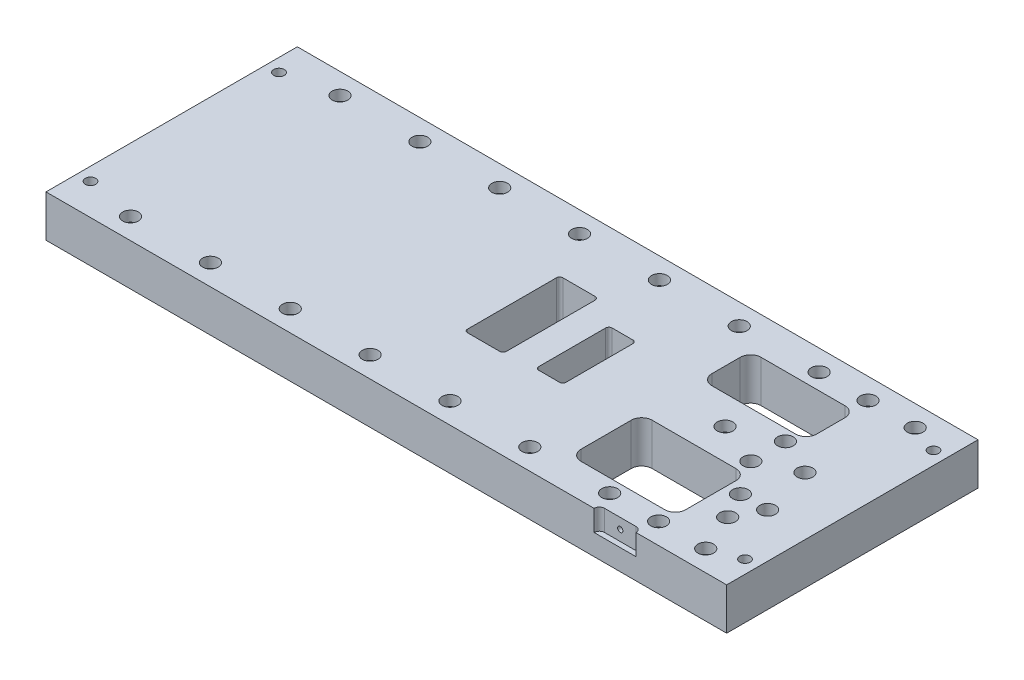
SolidWorks part; units mm, degrees
material "K110"
ref_plane "Front Plane" through (0, 0, 0) normal (0, 0, 1) x (1, 0, 0)
ref_plane "Top Plane" through (0, 0, 0) normal (0, 1, 0) x (1, 0, 0)
ref_plane "Right Plane" through (0, 0, 0) normal (1, 0, 0) x (0, 0, -1)
sketch "Sketch1" plane through (0, 0, 0) normal (0, 1, 0) x (1, 0, 0)
  line L1 (-325, -120) -> (325, -120)
  line L2 (-325, -120) -> (-325, 120)
  line L3 (-325, 120) -> (325, 120)
  line L4 (325, -120) -> (325, 120)
  line L5 (-325, -120) -> (325, 120) construction
  line L6 (-325, 120) -> (325, -120) construction
  point P0 (0, 0)
  dimension "D1" = 240
  dimension "D2" = 650
extrude "Boss-Extrude1" add sketch "Sketch1" against normal blind 40
sketch "Sketch2" plane through (0, 0, 0) normal (0, 1, 0) x (1, 0, 0)
  line L0 (187.25, -63.53) -> (187.25, -47.4) construction
  line L1 (184.25, -44.4) -> (180.25, -44.4) construction
  line L2 (174.25, -38.4) -> (174.25, -32.27) construction
  line L3 (174.25, -32.27) -> (172.25, -32.27) construction
  line L12 (169.25, -35.27) -> (169.25, -71.53) construction
  line L13 (172.25, -74.53) -> (214.25, -74.53) construction
  line L14 (199.25, -47.4) -> (199.25, -63.53) construction
  line L15 (206.25, -44.4) -> (202.25, -44.4) construction
  line L16 (212.25, -32.27) -> (212.25, -38.4) construction
  line L17 (214.25, -32.27) -> (212.25, -32.27) construction
  line L18 (217.25, -71.53) -> (217.25, -35.27) construction
  line L19 (187.25, -63.53) -> (187.25, -47.4)
  line L20 (184.25, -44.4) -> (180.25, -44.4)
  line L21 (174.25, -38.4) -> (174.25, -32.27)
  line L22 (174.25, -32.27) -> (172.25, -32.27)
  line L23 (169.25, -35.27) -> (169.25, -71.53)
  line L24 (172.25, -74.53) -> (214.25, -74.53)
  line L25 (199.25, -47.4) -> (199.25, -63.53)
  line L26 (206.25, -44.4) -> (202.25, -44.4)
  line L27 (212.25, -32.27) -> (212.25, -38.4)
  line L28 (214.25, -32.27) -> (212.25, -32.27)
  line L29 (217.25, -71.53) -> (217.25, -35.27)
  line L30 (212.25, 47.73) -> (214.25, 47.73) construction
  line L31 (212.25, 69.53) -> (212.25, 47.73) construction
  line L32 (174.25, 69.53) -> (212.25, 69.53) construction
  line L33 (174.25, 47.73) -> (174.25, 69.53) construction
  line L34 (172.25, 47.73) -> (174.25, 47.73) construction
  line L35 (169.25, 71.53) -> (169.25, 50.73) construction
  line L36 (214.25, 74.53) -> (172.25, 74.53) construction
  line L37 (217.25, 50.73) -> (217.25, 71.53) construction
  line L38 (212.25, 47.73) -> (214.25, 47.73)
  line L39 (212.25, 69.53) -> (212.25, 47.73)
  line L40 (174.25, 69.53) -> (212.25, 69.53)
  line L41 (174.25, 47.73) -> (174.25, 69.53)
  line L42 (172.25, 47.73) -> (174.25, 47.73)
  line L43 (169.25, 71.53) -> (169.25, 50.73)
  line L44 (214.25, 74.53) -> (172.25, 74.53)
  line L45 (217.25, 50.73) -> (217.25, 71.53)
  arc A0 (187.25, -47.4) -> (184.25, -44.4) centre (184.25, -47.4) ccw construction
  arc A1 (174.25, -38.4) -> (180.25, -44.4) centre (180.25, -38.4) ccw construction
  arc A2 (172.25, -32.27) -> (169.25, -35.27) centre (172.25, -35.27) ccw construction
  arc A3 (169.25, -71.53) -> (172.25, -74.53) centre (172.25, -71.53) ccw construction
  arc A4 (214.25, -74.53) -> (217.25, -71.53) centre (214.25, -71.53) ccw construction
  arc A5 (187.25, -63.53) -> (199.25, -63.53) centre (193.25, -63.53) ccw construction
  arc A6 (202.25, -44.4) -> (199.25, -47.4) centre (202.25, -47.4) ccw construction
  arc A7 (206.25, -44.4) -> (212.25, -38.4) centre (206.25, -38.4) ccw construction
  arc A8 (217.25, -35.27) -> (214.25, -32.27) centre (214.25, -35.27) ccw construction
  arc A9 (187.25, -47.4) -> (184.25, -44.4) centre (184.25, -47.4) ccw
  arc A10 (174.25, -38.4) -> (180.25, -44.4) centre (180.25, -38.4) ccw
  arc A11 (172.25, -32.27) -> (169.25, -35.27) centre (172.25, -35.27) ccw
  arc A12 (169.25, -71.53) -> (172.25, -74.53) centre (172.25, -71.53) ccw
  arc A13 (214.25, -74.53) -> (217.25, -71.53) centre (214.25, -71.53) ccw
  arc A14 (187.25, -63.53) -> (199.25, -63.53) centre (193.25, -63.53) ccw
  arc A15 (202.25, -44.4) -> (199.25, -47.4) centre (202.25, -47.4) ccw
  arc A16 (206.25, -44.4) -> (212.25, -38.4) centre (206.25, -38.4) ccw
  arc A17 (217.25, -35.27) -> (214.25, -32.27) centre (214.25, -35.27) ccw
  circle A18 centre (269.5, -63.53) radius 2.5 construction
  circle A19 centre (282.5, -38.4) radius 2.5 construction
  circle A20 centre (256.5, -38.4) radius 2.5 construction
  circle A21 centre (234.38, -6.27) radius 2.5 construction
  circle A22 centre (234.38, 26.73) radius 2.5 construction
  arc A23 (214.25, 47.73) -> (217.25, 50.73) centre (214.25, 50.73) ccw construction
  arc A24 (169.25, 50.73) -> (172.25, 47.73) centre (172.25, 50.73) ccw construction
  arc A25 (172.25, 74.53) -> (169.25, 71.53) centre (172.25, 71.53) ccw construction
  arc A26 (217.25, 71.53) -> (214.25, 74.53) centre (214.25, 71.53) ccw construction
  circle A27 centre (269.5, -63.53) radius 2.5
  circle A28 centre (282.5, -38.4) radius 2.5
  circle A29 centre (256.5, -38.4) radius 2.5
  circle A30 centre (234.38, -6.27) radius 2.5
  circle A31 centre (234.38, 26.73) radius 2.5
  arc A32 (214.25, 47.73) -> (217.25, 50.73) centre (214.25, 50.73) ccw
  arc A33 (169.25, 50.73) -> (172.25, 47.73) centre (172.25, 50.73) ccw
  arc A34 (172.25, 74.53) -> (169.25, 71.53) centre (172.25, 71.53) ccw
  arc A35 (217.25, 71.53) -> (214.25, 74.53) centre (214.25, 71.53) ccw
sketch "Sketch3" plane through (0, 0, 0) normal (0, 1, 0) x (1, 0, 0)
  line L1 (153.25, 84.63) -> (233.25, 84.63)
  line L2 (143.25, 74.63) -> (143.25, 47.63)
  line L3 (153.25, 37.63) -> (233.25, 37.63)
  line L4 (243.25, 74.63) -> (243.25, 47.63)
  line L8 (169.25, -53.4) -> (217.25, -53.4) construction
  line L9 (153.25, -19.4) -> (233.25, -19.4)
  line L10 (143.25, -29.4) -> (143.25, -77.4)
  line L11 (153.25, -87.4) -> (233.25, -87.4)
  line L12 (243.25, -29.4) -> (243.25, -77.4)
  line L13 (169.25, -35.27) -> (169.25, -71.53) construction
  line L14 (217.25, -71.53) -> (217.25, -35.27) construction
  line L15 (193.25, -74.53) -> (193.25, -19.4) construction
  line L16 (172.25, -74.53) -> (214.25, -74.53) construction
  line L17 (193.25, 84.63) -> (193.25, 47.73) construction
  line L18 (169.25, 61.13) -> (217.25, 61.13) construction
  line L19 (169.25, 71.53) -> (169.25, 50.73) construction
  line L20 (217.25, 50.73) -> (217.25, 71.53) construction
  arc A0 (143.25, 47.63) -> (153.25, 37.63) centre (153.25, 47.63) ccw
  arc A1 (233.25, 37.63) -> (243.25, 47.63) centre (233.25, 47.63) ccw
  arc A2 (243.25, 74.63) -> (233.25, 84.63) centre (233.25, 74.63) ccw
  arc A3 (153.25, 84.63) -> (143.25, 74.63) centre (153.25, 74.63) ccw
  circle A4 centre (234.38, 26.73) radius 7.5
  circle A5 centre (234.38, -6.27) radius 7.5
  circle A6 centre (269.5, -63.53) radius 7.5
  circle A7 centre (282.5, -38.4) radius 7.5
  circle A8 centre (256.5, -38.4) radius 7.5
  arc A9 (143.25, -77.4) -> (153.25, -87.4) centre (153.25, -77.4) ccw
  arc A10 (233.25, -87.4) -> (243.25, -77.4) centre (233.25, -77.4) ccw
  arc A11 (243.25, -29.4) -> (233.25, -19.4) centre (233.25, -29.4) ccw
  arc A12 (153.25, -19.4) -> (143.25, -29.4) centre (153.25, -29.4) ccw
  dimension "D5" = 10
  dimension "D6" = 15
  dimension "D11" = 10
  dimension "D2" = 100
  dimension "D3" = 47
  dimension "D7" = 68
  dimension "D8" = 100
extrude "Cut-Extrude2" cut sketch "Sketch3" against normal up to next
sketch "Sketch4" plane through (0, -40, 0) normal (0, -1, 0) x (1, 0, 0)
  circle A0 centre (234.38, -26.73) radius 9
  circle A1 centre (234.38, 6.27) radius 9
  circle A2 centre (256.5, 38.4) radius 9
  circle A3 centre (282.5, 38.4) radius 9
  circle A4 centre (269.5, 63.53) radius 9
  dimension "D1" = 18
extrude "Cut-Extrude3" cut sketch "Sketch4" against normal blind 5
extrude "Cut-Extrude9" cut sketch "Sketch11" against normal through all
sketch "Sketch11" plane through (304.63, 0, 0) normal (0, 1, 0) x (1, 0, 0)
  circle A0 centre (-35.13, 10.23) radius 7.5
  circle A1 centre (-111.38, 10.23) radius 7.5
extrude "Cut-Extrude10" cut sketch "Sketch12" against normal blind 5
sketch "Sketch12" plane through (304.63, -40, 0) normal (0, -1, 0) x (1, 0, 0)
  circle A0 centre (-35.13, -10.23) radius 10
extrude "Cut-Extrude11" cut sketch "Sketch13" against normal blind 30
sketch "Sketch13" plane through (304.63, -40, 0) normal (0, -1, 0) x (1, 0, 0)
  circle A0 centre (-111.38, -10.23) radius 10
hole_wizard "M10 Tapped Hole1" positions "Sketch27" profile "Sketch15" tap size "M10" standard "ISO"
sketch "Sketch27" plane through (0, -40, 0) normal (0, -1, 0) x (-1, 0, 0)
  line L0 (-325, -120) -> (-325, 120) construction
  line L1 (-325, 120) -> (325, 120) construction
  line L2 (325, 120) -> (325, -120) construction
  line L3 (325, -120) -> (-325, -120) construction
  point P0 (-312.5, 107.5)
  point P2 (312.5, 107.5)
  point P4 (312.5, -107.5)
  point P6 (-312.5, -107.5)
  dimension "D1" = 12.5
  dimension "D2" = 12.5
  dimension "D3" = 12.5
  dimension "D4" = 12.5
sketch "Sketch15" plane through (312.5, -40, -107.5) normal (1, 0, 0) x (0, 0, -1)
  line L0 (0, 0) -> (0, 30.0537)
  line L1 (0, 30.0537) -> (4.25, 27.5)
  line L2 (4.25, 27.5) -> (4.25, 0.775)
  line L3 (4.25, 0.775) -> (5.025, 0)
  line L5 (5.025, 0) -> (0, 0)
  line L6 (-4.25, 0.775) -> (-5.025, 0) construction
  line L10 (0, 30.0537) -> (-4.25, 27.5) construction
  line L11 (0, -6.35) -> (0, 107.95) construction
  dimension "Tap Drill Dia." = 8.5
  dimension "Tap Drill Depth" = 27.5
  dimension "Near C'Sink Dia." = 10.05
  dimension "Near C'Sink Angle" = 90
  dimension "Drill Angle" = 118
cosmetic thread "Hole Thread1" parameters "D1"=20, "D2"=10
cosmetic thread "Hole Thread2" parameters "D1"=20, "D2"=10
cosmetic thread "Hole Thread3" parameters "D1"=20, "D2"=10
cosmetic thread "Hole Thread4" parameters "D1"=20, "D2"=10
hole_wizard "Ø10.0mm Dowel Hole2" positions "Sketch26" profile "Sketch25" hole size "Ø10.0" standard "ISO" end condition through all
sketch "Sketch26" plane through (0, -40, 0) normal (0, -1, 0) x (-1, 0, 0)
  line L0 (-325, -120) -> (-325, 120) construction
  line L1 (325, 120) -> (325, -120) construction
  circle A0 centre (-312.5, 107.5) radius 4.25 construction
  circle A1 centre (-312.5, -107.5) radius 4.25 construction
  point P0 (-312.5, 90)
  point P2 (312.5, 90)
  point P4 (312.5, -90)
  point P6 (-312.5, -90)
  dimension "D4" = 17.5
  dimension "D1" = 12.5
  dimension "D2" = 17.5
  dimension "D3" = 12.5
sketch "Sketch25" plane through (312.5, -40, -90) normal (1, 0, 0) x (0, 0, -1)
  line L0 (0, 0) -> (0, 40)
  line L1 (0, 40) -> (5, 40)
  line L2 (5, 40) -> (5, 0)
  line L5 (5, 0) -> (0, 0)
  line L11 (0, -6.35) -> (0, 107.95) construction
  dimension "Thru Hole Dia." = 10
  dimension "Thru Hole Depth" = 40
sketch "Sketch28" plane through (0, 0, 0) normal (0, 1, 0) x (1, 0, 0)
  line L0 (-164, -95) -> (304.63, -95) construction
  line L2 (325, -120) -> (325, 120) construction
  circle A0 centre (240, -100) radius 7.5
  circle A1 centre (285, -100) radius 7.5
  circle A2 centre (117, -100) radius 7.5
  circle A3 centre (40.75, -100) radius 7.5
  circle A4 centre (193.25, -100) radius 7.5
  circle A5 centre (-35.5, -100) radius 7.5
  circle A6 centre (-111.75, -100) radius 7.5
  circle A7 centre (-188, -100) radius 7.5
  circle A8 centre (-264.25, -100) radius 7.5
  dimension "D1" = 15
  dimension "D2" = 5
  dimension "D3" = 46.75
  dimension "D4" = 40
  dimension "D5" = 45
  dimension "D7" = 76.25
  dimension "D6" = 7
extrude "Cut-Extrude12" cut sketch "Sketch28" against normal up to next
mirror "Mirror1" about plane through (0, 0, 0) normal (0, 0, 1) of "Cut-Extrude12"
sketch "Sketch29" plane through (0, -40, 0) normal (0, -1, 0) x (1, 0, 0)
  circle A0 centre (193.25, 100) radius 9
  circle A1 centre (240, 100) radius 9
  circle A2 centre (240, -100) radius 9
  circle A3 centre (193.25, -100) radius 9
  circle A4 centre (285, 100) radius 9
  circle A5 centre (285, -100) radius 9
  circle A6 centre (117, 100) radius 9
  circle A7 centre (117, -100) radius 9
  circle A8 centre (40.75, 100) radius 9
  circle A9 centre (40.75, -100) radius 9
  circle A10 centre (-35.5, 100) radius 9
  circle A11 centre (-35.5, -100) radius 9
  circle A12 centre (-111.75, 100) radius 9
  circle A13 centre (-111.75, -100) radius 9
  circle A14 centre (-188, 100) radius 9
  circle A15 centre (-188, -100) radius 9
  circle A16 centre (-264.25, 100) radius 9
  circle A17 centre (-264.25, -100) radius 9
  dimension "D1" = 18
  dimension "D2" = 7
extrude "Cut-Extrude13" cut sketch "Sketch29" against normal blind 30
extrude "Cut-Extrude14" cut sketch "Sketch30" against normal blind 20
sketch "Sketch30" plane through (304.63, 0, 0) normal (0, 1, 0) x (1, 0, 0)
  line L1 (-106.25, -120) -> (-66.25, -120)
  line L3 (-101.25, -115) -> (-71.25, -115)
  arc A0 (-106.25, -120) -> (-101.25, -115) centre (-101.25, -120) cw
  arc A1 (-66.25, -120) -> (-71.25, -115) centre (-71.25, -120) ccw
hole_wizard "M6 Tapped Hole1" positions "Sketch37" profile "Sketch32" tap size "M6" standard "ISO"
sketch "Sketch37" plane through (0, 0, 115) normal (0, 0, 1) x (1, 0, 0)
  line L4 (218.38, -20) -> (218.38, 0) construction
  line L5 (198.38, -20) -> (238.38, -20) construction
  line L6 (233.38, 0) -> (203.38, 0) construction
  line L7 (132, 0) -> (-132, 0) construction
  point P2 (218.38, -10)
  dimension "D1" = 10
sketch "Sketch32" plane through (218.38, -10, 115) normal (1, 0, 0) x (0, -1, 0)
  line L0 (0, 0) -> (0, 11.5022)
  line L1 (0, 11.5022) -> (2.5, 10)
  line L2 (2.5, 10) -> (2.5, 0)
  line L5 (2.5, 0) -> (0, 0)
  line L10 (0, 11.5022) -> (-2.5, 10) construction
  line L11 (0, -6.35) -> (0, 107.95) construction
  dimension "Tap Drill Dia." = 5
  dimension "Tap Drill Depth" = 10
  dimension "Drill Angle" = 118
cosmetic thread "Hole Thread5" parameters "D1"=8, "D2"=6
sketch "Sketch38" plane through (0, 0, 0) normal (0, 1, 0) x (1, 0, 0)
  line L0 (75.88, -10.27) -> (75.88, 15.73) construction
  line L1 (57.75, -32.27) -> (77.75, -32.27)
  line L2 (54.75, -29.27) -> (54.75, 34.73)
  line L3 (57.75, 37.73) -> (77.75, 37.73)
  line L4 (80.75, -29.27) -> (80.75, 34.73)
  line L5 (72.88, 18.73) -> (59.75, 18.73) construction
  line L6 (59.75, -11.27) -> (59.75, -13.27) construction
  line L7 (59.75, -13.27) -> (72.88, -13.27) construction
  arc A1 (57.75, -32.27) -> (54.75, -29.27) centre (57.75, -29.27) cw
  arc A2 (77.75, -32.27) -> (80.75, -29.27) centre (77.75, -29.27) ccw
  arc A3 (77.75, 37.73) -> (80.75, 34.73) centre (77.75, 34.73) cw
  arc A4 (54.75, 34.73) -> (57.75, 37.73) centre (57.75, 34.73) cw
  point P18 (80.75, 37.73)
  point P21 (54.75, 37.73)
  dimension "D7" = 3
  dimension "D1" = 4.87
  dimension "D2" = 19
  dimension "D3" = 5
  dimension "D4" = 19
  dimension "D5" = 70
  dimension "D6" = 26
extrude "Cut-Extrude15" cut sketch "Sketch38" against normal up to next
sketch "Sketch39" plane through (0, 0, 0) normal (0, 1, 0) x (1, 0, 0)
  line L0 (-5.37, 11.73) -> (-5.37, -6.27) construction
  line L1 (-7.25, -35.27) -> (23.75, -35.27)
  line L2 (-10.25, -32.27) -> (-10.25, 52.73)
  line L3 (-7.25, 55.73) -> (23.75, 55.73)
  line L4 (26.75, -32.27) -> (26.75, 52.73)
  line L5 (21.75, -17.27) -> (21.75, -13.77) construction
  line L6 (-2.37, -17.27) -> (21.75, -17.27) construction
  line L7 (21.75, 37.73) -> (-2.37, 37.73) construction
  arc A0 (23.75, 55.73) -> (26.75, 52.73) centre (23.75, 52.73) cw
  arc A1 (-10.25, 52.73) -> (-7.25, 55.73) centre (-7.25, 52.73) cw
  arc A2 (-7.25, -35.27) -> (-10.25, -32.27) centre (-7.25, -32.27) cw
  arc A3 (23.75, -35.27) -> (26.75, -32.27) centre (23.75, -32.27) ccw
  point P14 (26.75, 55.73)
  point P17 (-10.25, 55.73)
  point P22 (26.75, -35.27)
  dimension "D7" = 3
  dimension "D1" = 4.88
  dimension "D2" = 5
  dimension "D3" = 18
  dimension "D4" = 18
  dimension "D5" = 91
  dimension "D6" = 37
extrude "Cut-Extrude16" cut sketch "Sketch39" against normal up to next
